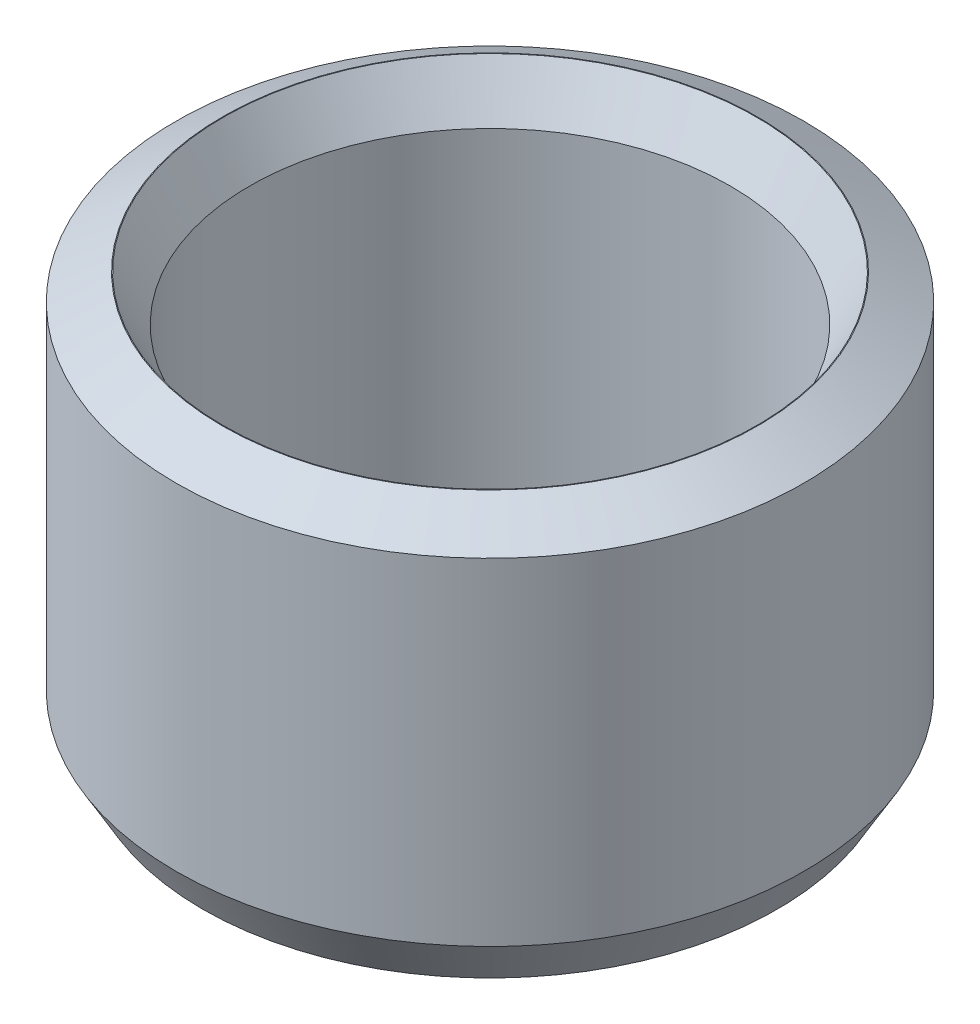
SolidWorks part; units mm, degrees
ref_plane "Front Plane" through (0, 0, 0) normal (0, 0, 1) x (1, 0, 0)
ref_plane "Top Plane" through (0, 0, 0) normal (0, 1, 0) x (1, 0, 0)
ref_plane "Right Plane" through (0, 0, 0) normal (1, 0, 0) x (0, 0, -1)
sketch "Sketch1" plane through (0, 0, 0) normal (0, 1, 0) x (1, 0, 0)
  circle A0 centre (0, 0) radius 35
  dimension "SLEEVE_OD" = 70
extrude "Boss-Extrude1" add sketch "Sketch1" along normal blind 45.615
sketch "Sketch2" plane through (0, 0, 0) normal (0, 1, 0) x (1, 0, 0)
  circle A0 centre (0, 0) radius 26.8049
  dimension "BORE_D" = 53.6097
extrude "Cut-Extrude1" cut sketch "Sketch2" along normal through all
chamfer "Chamfer1" distance 2.9688 angle 60 4 edges at (0, 45.615, 26.8049) (0, 0, 26.8049) (0, 0, 35) (0, 45.615, 35) first distance on face at (0, 45.615, 26.8049) first distance on face at (0, 0, 26.8049) first distance on face at (0, 45.615, 35)
